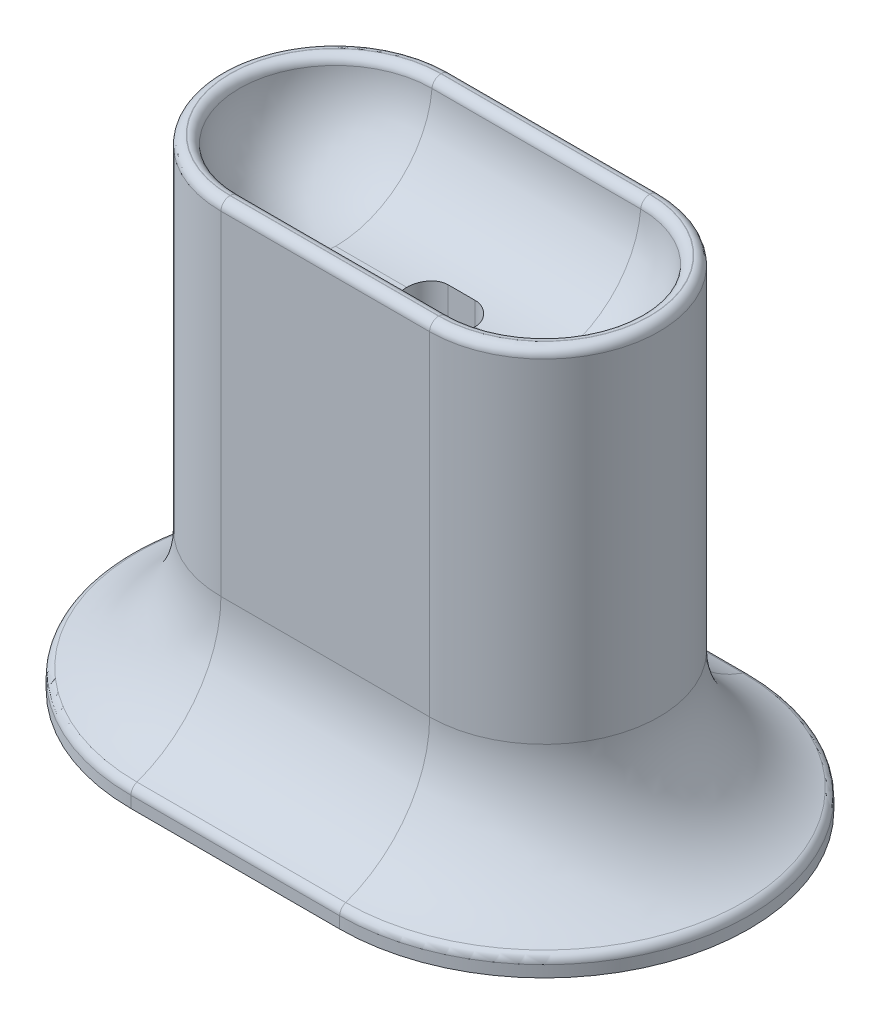
SolidWorks part; units mm, degrees
ref_plane "Front Plane" through (0, 0, 0) normal (0, 0, 1) x (1, 0, 0)
ref_plane "Top Plane" through (0, 0, 0) normal (0, 1, 0) x (1, 0, 0)
ref_plane "Right Plane" through (0, 0, 0) normal (1, 0, 0) x (0, 0, -1)
sketch "Sketch2" plane through (0, 0, 0) normal (0, 1, 0) x (1, 0, 0)
  line L0 (0, 10.75) -> (23.2, 10.75)
  line L1 (0, -10.75) -> (23.2, -10.75)
  line L2 (0, -12.75) -> (23.2, -12.75)
  line L3 (0, 12.75) -> (23.2, 12.75)
  line L4 (0, 22.75) -> (23.2, 22.75)
  line L5 (0, -22.75) -> (23.2, -22.75)
  arc A0 (0, 10.75) -> (0, -10.75) centre (0, 0) ccw
  arc A1 (23.2, -10.75) -> (23.2, 10.75) centre (23.2, 0) ccw
  arc A2 (0, 12.75) -> (0, -12.75) centre (0, 0) ccw
  arc A3 (23.2, -12.75) -> (23.2, 12.75) centre (23.2, 0) ccw
  arc A4 (23.2, -22.75) -> (23.2, 22.75) centre (23.2, 0) ccw
  arc A5 (0, 22.75) -> (0, -22.75) centre (0, 0) ccw
  dimension "D1" = 21.5
  dimension "D2" = 23.2
  dimension "D3" = 2
  dimension "D4" = 10
extrude "Boss-Extrude1" add sketch "Sketch2" along normal blind 53.5 contours L2 A3 L3 A2 A1 L1 A0 L0 region at (-12.2003, 0, 0)
extrude "Boss-Extrude2" add sketch "Sketch2<3>" against normal blind 10 from offset 42.75 contours L1 A1 L0 A0 region at (11.6, 0, 0)
sketch "Sketch2<3>" plane through (0, 0, 0) normal (0, 1, 0) x (1, 0, 0) same geometry as "Sketch2"
extrude "Boss-Extrude3" add sketch "Sketch2<4>" along normal blind 2 contours L4 A5 L5 A4 A3 L2 A2 L3 region at (11.6, 0, -21.926)
sketch "Sketch2<4>" plane through (0, 0, 0) normal (0, 1, 0) x (1, 0, 0) same geometry as "Sketch2"
fillet "Fillet1" radius 10.75 4 edges at (11.6, 42.75, -10.75) (33.95, 42.75, 0) (11.6, 42.75, 10.75) (-10.75, 42.75, 0)
fillet "Fillet2" radius 14 4 edges at (-12.75, 2, 0) (11.6, 2, -12.75) (35.95, 2, 0) (11.6, 2, 12.75)
fillet "Fillet3" radius 1 12 edges at (-22.75, 2, 0) (11.6, 2, 22.75) (45.95, 2, 0) (-10.75, 53.5, 0) (11.6, 53.5, 10.75) (33.95, 53.5, 0) (-12.75, 53.5, 0) (11.6, 53.5, 12.75) (35.95, 53.5, 0) (11.6, 2, -22.75) (11.6, 53.5, -10.75) (11.6, 53.5, -12.75)
sketch "Sketch3" plane through (0, 32.75, 0) normal (0, -1, 0) x (1, 0, 0)
  line L0 (10.2, 2.3) -> (13.2, 2.3)
  line L1 (10.2, -2.3) -> (13.2, -2.3)
  arc A0 (10.2, 2.3) -> (10.2, -2.3) centre (10.2, 0) ccw
  arc A1 (13.2, -2.3) -> (13.2, 2.3) centre (13.2, 0) ccw
  arc A2 (23.2, -10.75) -> (23.2, 10.75) centre (23.2, 0) ccw construction
  point P1 (15.5, 0)
  point P10 (33.95, 0)
  dimension "D1" = 4.6
  dimension "D2" = 3
  dimension "D3" = 18.45
extrude "Cut-Extrude1" cut sketch "Sketch3" against normal through all both and the other way through all
sketch "Sketch4" plane through (0, 0, -10.75) normal (0, 0, 1) x (1, 0, 0)
  line L0 (0, 2.2171) -> (23.2, 2.2171) construction
  line L3 (10.6, 1.099) -> (10.6, 0)
  line L4 (12.6, 1.099) -> (12.6, 0)
  line L7 (10.6, 0) -> (12.6, 0)
  arc A0 (12.6, 1.099) -> (10.6, 1.099) centre (11.6, 2.2171) ccw
  dimension "D1" = 3
extrude "Cut-Extrude2" cut sketch "Sketch4" against normal through all
